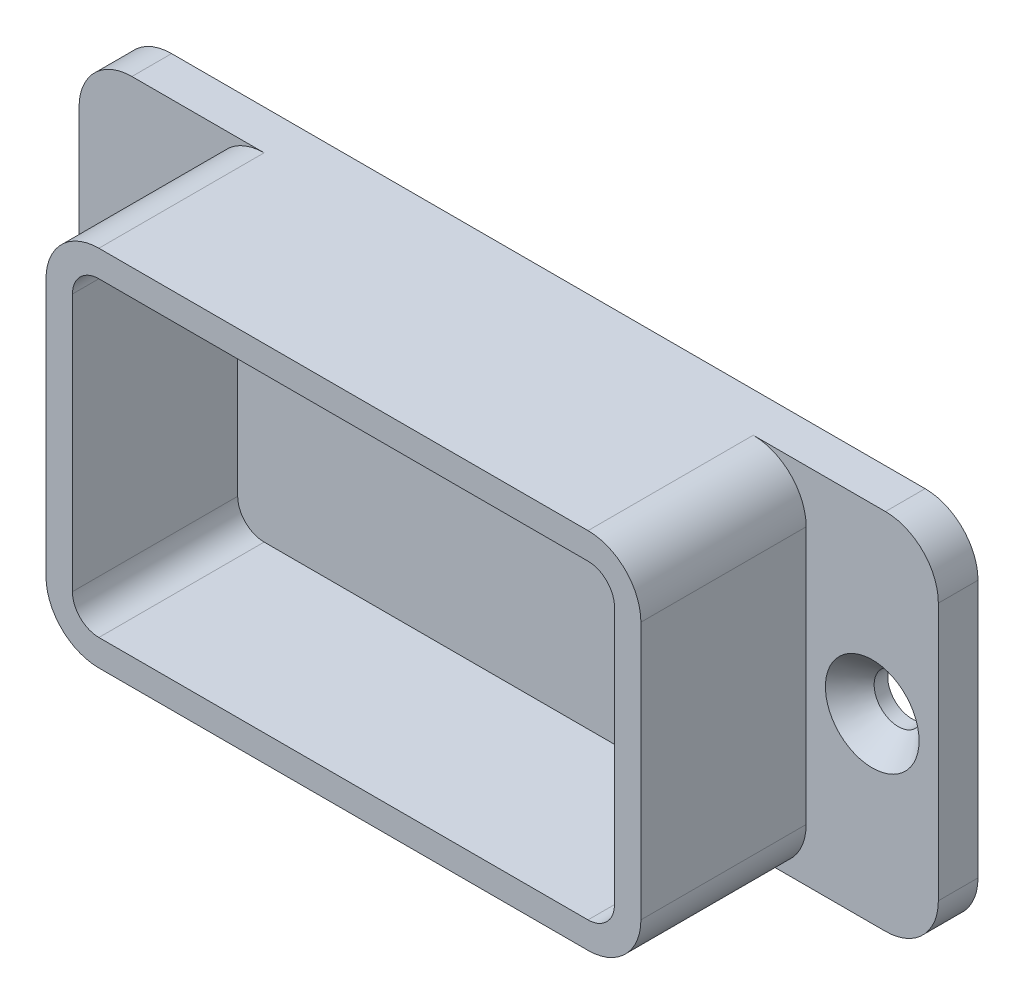
SolidWorks part; units mm, degrees
ref_plane "Front Plane" through (0, 0, 0) normal (0, 0, 1) x (1, 0, 0)
ref_plane "Top Plane" through (0, 0, 0) normal (0, 1, 0) x (1, 0, 0)
ref_plane "Right Plane" through (0, 0, 0) normal (1, 0, 0) x (0, 0, -1)
ref_plane "Bottom Plane" through (0, 0, -2.5) normal (0, 0, 1) x (1, 0, 0)
ref_plane "Top of Walls Plane" through (0, 0, 13) normal (0, 0, 1) x (1, 0, 0)
sketch "Walls Sketch" plane through (0, 0, -2.5) normal (0, 0, 1) x (1, 0, 0)
  line L1 (-20.5, -11.75) -> (20.5, -11.75)
  line L2 (-20.5, -11.75) -> (-20.5, 11.75)
  line L3 (-20.5, 11.75) -> (20.5, 11.75)
  line L4 (20.5, -11.75) -> (20.5, 11.75)
  line L5 (-20.5, -11.75) -> (20.5, 11.75) construction
  line L6 (-20.5, 11.75) -> (20.5, -11.75) construction
  line L7 (-22.5, -13.75) -> (22.5, -13.75)
  line L8 (-22.5, -13.75) -> (-22.5, 13.75)
  line L9 (-22.5, 13.75) -> (22.5, 13.75)
  line L10 (22.5, -13.75) -> (22.5, 13.75)
  line L11 (-22.5, -13.75) -> (22.5, 13.75) construction
  line L12 (-22.5, 13.75) -> (22.5, -13.75) construction
  point P0 (0, 0)
  point P6 (0, 0)
  dimension "D1" = 45
  dimension "D2" = 27.5
extrude "Walls Extrude" add sketch "Walls Sketch" along normal up to surface (15.5 mm away) up to plane "Top of Walls Plane"
sketch "Base Sketch" plane through (0, 0, -2.5) normal (0, 0, 1) x (1, 0, 0)
  line L0 (-22.5, -13.75) -> (22.5, -13.75) construction
  line L1 (-32.5, 13.75) -> (32.5, 13.75)
  line L2 (-32.5, 13.75) -> (-32.5, -13.75)
  line L3 (-32.5, -13.75) -> (32.5, -13.75)
  line L4 (32.5, 13.75) -> (32.5, -13.75)
  line L5 (22.5, 13.75) -> (-22.5, 13.75) construction
  line L6 (-22.5, 13.75) -> (-22.5, -13.75) construction
  line L7 (22.5, -13.75) -> (22.5, 13.75) construction
extrude "Base Extrude" add sketch "Base Sketch" along normal blind 3
hole_wizard "Mounting Holes" positions "Mounting Holes Position Sketch" profile "Mounting Holes Profile Sketch" countersink size "#6" standard "ANSI Inch" end condition through all
sketch "Mounting Holes Position Sketch" plane through (0, 0, 0.5) normal (0, 0, 1) x (1, 0, 0)
  line L0 (-32.5, 13.75) -> (-22.5, -13.75) construction
  line L2 (22.5, -13.75) -> (32.5, 13.75) construction
  line L3 (22.5, -13.75) -> (32.5, -13.75) construction
  point P0 (-27.5, 0)
  point P19 (27.5, 0)
  point P20 (0, 0)
  point P21 (24.2693, -10)
  point P25 (0, 0)
  point P26 (-24.9415, -10)
  point P27 (0, 0)
  point P28 (0, 0)
sketch "Mounting Holes Profile Sketch" plane through (-27.5, 0, 0.5) normal (1, 0, 0) x (0, -1, 0)
  line L0 (0, 0) -> (0, 3)
  line L1 (0, 3) -> (1.8288, 3)
  line L2 (1.8288, 3) -> (1.8288, 1.9723)
  line L3 (1.8288, 1.9723) -> (3.5433, 0)
  line L5 (3.5433, 0) -> (0, 0)
  line L6 (-1.8288, 1.9723) -> (-3.5433, 0) construction
  line L11 (0, -6.35) -> (0, 107.95) construction
  dimension "Thru Hole Dia." = 3.6576
  dimension "Thru Hole Depth" = 3
  dimension "Near C'Sink Dia." = 7.0866
  dimension "Near C'Sink Angle" = 82
fillet "Tab Fillets" radius 4 4 edges at (32.5, 13.75, -1) (32.5, -13.75, -1) (-32.5, 13.75, -1) (-32.5, -13.75, -1)
fillet "Inside Corner Fillets" radius 2 4 edges at (-20.5, -11.75, 6.75) (20.5, -11.75, 6.75) (20.5, 11.75, 6.75) (-20.5, 11.75, 6.75)
fillet "Outside Corner Fillets" radius 4 4 edges at (-22.5, 13.75, 6.75) (22.5, 13.75, 6.75) (22.5, -13.75, 6.75) (-22.5, -13.75, 6.75)
